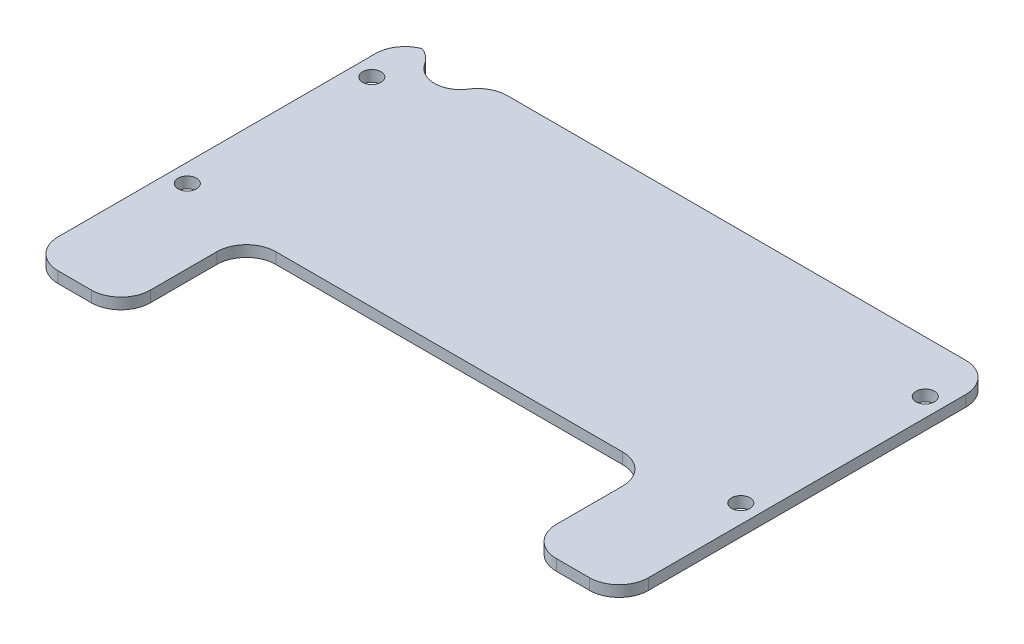
SolidWorks part; units mm, degrees
material "3.0205 (EN-AW 1200)"
ref_plane "Plan de face" through (0, 0, 0) normal (0, 0, 1) x (1, 0, 0)
ref_plane "Plan de dessus" through (0, 0, 0) normal (0, 1, 0) x (1, 0, 0)
ref_plane "Plan de droite" through (0, 0, 0) normal (1, 0, 0) x (0, 0, -1)
sketch "Esquisse1" plane through (0, 0, 0) normal (0, 1, 0) x (1, 0, 0)
  line L1 (-40, -51) -> (40, -51)
  line L2 (-40, -51) -> (-40, 0)
  line L3 (-40, 0) -> (40, 0)
  line L4 (40, -51) -> (40, 0)
  dimension "D1" = 80
  dimension "D2" = 51
extrude "Boss.-Extru.1" add sketch "Esquisse1" along normal blind 1.5
sketch "Esquisse2" plane through (0, 1.5, 0) normal (0, 1, 0) x (1, 0, 0)
  line L0 (-40, -51) -> (40, -51) construction
  line L1 (-27.5, -51) -> (27.5, -51)
  line L2 (-27.5, -51) -> (-27.5, -34)
  line L3 (-27.5, -34) -> (27.5, -34)
  line L4 (27.5, -51) -> (27.5, -34)
  line L5 (0, -34) -> (0, 0) construction
  line L6 (40, 0) -> (-40, 0) construction
  line L7 (-40, 0) -> (-40, -51) construction
  line L8 (-36, 0) -> (-29, 0)
  circle A0 centre (-37.5, -32) radius 1.25
  circle A1 centre (-37.5, -7) radius 1.25
  arc A2 (-36, 0) -> (-29, 0) centre (-32.5, 0) ccw
  circle A4 centre (37.5, -7) radius 1.25
  circle A5 centre (37.5, -32) radius 1.25
  point P4 (0, -51)
  point P18 (0, 0)
  dimension "D1" = 2.5
  dimension "D2" = 19
  dimension "D3" = 17
  dimension "D4" = 25
  dimension "D5" = 7
  dimension "D6" = 4
  dimension "D7" = 2.5
  dimension "D8" = 12.5
extrude "Enlèv. mat.-Extru.1" cut sketch "Esquisse2" against normal through all
fillet "Congé1" radius 4 10 edges at (-40, 0.75, 0) (27.5, 0.75, 34) (40, 0.75, 0) (40, 0.75, 51) (27.5, 0.75, 51) (-27.5, 0.75, 34) (-27.5, 0.75, 51) (-40, 0.75, 51) (-29, 0.75, 0) (-36, 0.75, 0)
